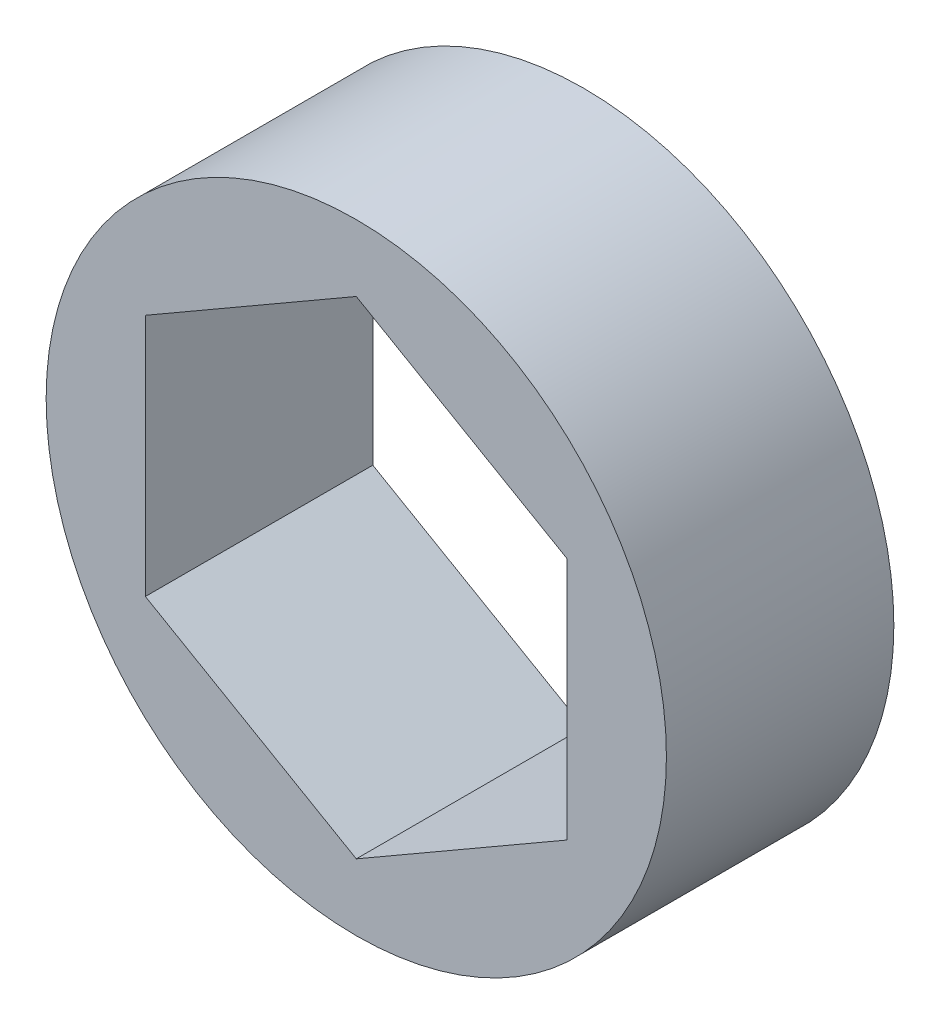
SolidWorks part; units mm, degrees
material "PET"
ref_plane "Front Plane" through (0, 0, 0) normal (0, 0, 1) x (1, 0, 0)
ref_plane "Top Plane" through (0, 0, 0) normal (0, 1, 0) x (1, 0, 0)
ref_plane "Right Plane" through (0, 0, 0) normal (1, 0, 0) x (0, 0, -1)
sketch "Sketch1" plane through (0, 0, 0) normal (0, 0, 1) x (1, 0, 0)
  line L1 (0, 7.479) -> (-6.477, 3.7395)
  line L2 (-6.477, 3.7395) -> (-6.477, -3.7395)
  line L3 (-6.477, -3.7395) -> (0, -7.479)
  line L4 (0, -7.479) -> (6.477, -3.7395)
  line L5 (6.477, -3.7395) -> (6.477, 3.7395)
  line L6 (6.477, 3.7395) -> (0, 7.479)
  circle A0 centre (0, 0) radius 6.477 construction
  circle A1 centre (0, 0) radius 9.525
  dimension "D1" = 12.954
  dimension "D2" = 19.05
extrude "Boss-Extrude1" add sketch "Sketch1" along normal mid plane 6.985
